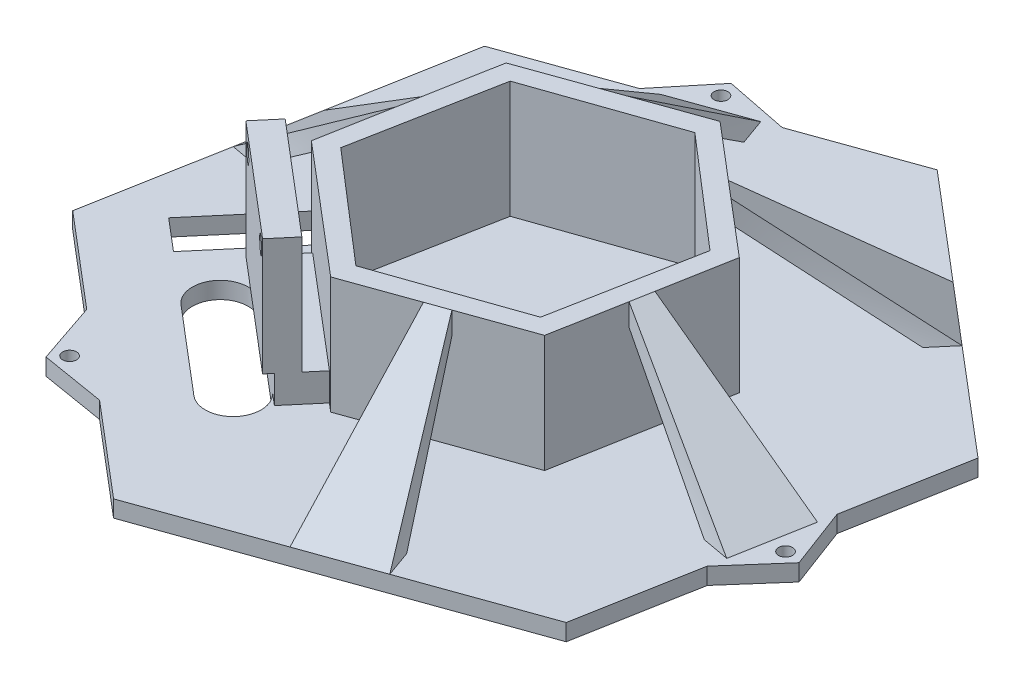
SolidWorks part; units mm, degrees
material "ABS"
ref_plane "Plan de face" through (0, 0, 0) normal (0, 0, 1) x (1, 0, 0)
ref_plane "Plan de dessus" through (0, 0, 0) normal (0, 1, 0) x (1, 0, 0)
ref_plane "Plan de droite" through (0, 0, 0) normal (1, 0, 0) x (0, 0, -1)
sketch "Esquisse1" plane through (0, 0, 0) normal (0, 1, 0) x (1, 0, 0)
  line L0 (-54.0644, 46.7159) -> (42.7784, -35.4763)
  line L1 (-54.0644, 46.7159) -> (-33.5846, 54.0399)
  line L2 (-54.0644, 46.7159) -> (-65.444, -15.7663)
  line L3 (-65.444, -15.7663) -> (-17.0226, -56.8624)
  line L4 (-17.0226, -56.8624) -> (42.7784, -35.4763)
  line L5 (42.7784, -35.4763) -> (54.1579, 27.0059)
  line L6 (54.1579, 27.0059) -> (5.7365, 68.102)
  line L7 (5.7365, 68.102) -> (-54.0644, 46.7159)
  line L8 (5.7365, 68.102) -> (-14.7432, 60.778)
  line L9 (-65.444, -15.7663) -> (-48.8613, -29.8403)
  line L10 (-17.0226, -56.8624) -> (-33.6053, -42.7884)
  line L11 (54.1579, 27.0059) -> (50.2608, 5.6079)
  line L12 (42.7784, -35.4763) -> (46.6755, -14.0783)
  line L13 (46.6755, -14.0783) -> (50.2608, 5.6079)
  line L14 (46.6755, -14.0783) -> (48.4681, -4.2352)
  line L15 (48.4681, -4.2352) -> (54.371, -5.3102)
  line L16 (54.371, -5.3102) -> (50.2608, 5.6079)
  line L17 (54.371, -5.3102) -> (46.6755, -14.0783)
  line L18 (-33.5846, 54.0399) -> (-24.1639, 57.409)
  line L19 (-24.1639, 57.409) -> (-26.1844, 63.0586)
  line L20 (-14.7432, 60.778) -> (-26.1844, 63.0586)
  line L21 (-33.5846, 54.0399) -> (-26.1844, 63.0586)
  line L22 (-48.8613, -29.8403) -> (-41.2333, -36.3143)
  line L23 (-41.2333, -36.3143) -> (-45.1158, -40.8889)
  line L24 (-45.1158, -40.8889) -> (-33.6053, -42.7884)
  line L25 (-45.1158, -40.8889) -> (-48.8613, -29.8403)
  line L26 (-24.1639, 57.409) -> (-25.1741, 60.2338)
  line L27 (48.4681, -4.2352) -> (51.4196, -4.7727)
  line L28 (-41.2333, -36.3143) -> (-43.1745, -38.6016)
  circle A0 centre (-5.643, 5.6198) radius 55.0013 construction
  circle A1 centre (-25.1741, 60.2338) radius 1.25
  circle A2 centre (51.4196, -4.7727) radius 1.25
  circle A3 centre (-43.1745, -38.6016) radius 1.25
extrude "Boss.-Extru.2" add sketch "Esquisse1" along normal blind 3 contours L3 L4 L0 L2 | A3 L23 L3 L25 | A3 L23 L24 L3 | L6 L7 L1 L0 L5 L13 | A2 L15 L16 L13 | A2 L15 L5 L17 | A1 L19 L7 L20 | A1 L19 L21 L7 region at (10.1749, 0, -24.2572) region at (-21.4609, 0, 13.0176) region at (-28.1828, 0, -58.0012) region at (49.7059, 0, 8.1043) region at (-21.432, 0, -60.4154) region at (-45.2029, 0, 35.4517) region at (-39.7367, 0, 40.0909) region at (50.9905, 0, 1.0508)
sketch "Esquisse2" plane through (0, 3, 0) normal (0, 1, 0) x (1, 0, 0)
  line L0 (-48.8613, -29.8403) -> (-65.444, -15.7663)
  line L1 (-65.444, -15.7663) -> (-17.0226, -56.8624)
  line L2 (-48.8613, -29.8403) -> (-41.0964, -20.6912)
  line L3 (-33.6053, -42.7884) -> (-25.8403, -33.6393)
  line L4 (-41.0964, -20.6912) -> (-25.8403, -33.6393)
  line L5 (-41.0964, -20.6912) -> (-34.6255, -13.067)
  line L6 (-25.8403, -33.6393) -> (-19.3695, -26.0151)
  line L7 (-34.6255, -13.067) -> (-19.3695, -26.0151)
  line L8 (-41.0964, -20.6912) -> (-48.8613, -29.8403)
  line L10 (-48.8613, -29.8403) -> (-65.444, -15.7663)
  line L11 (-41.6731, -13.6437) -> (-18.7928, -33.0626)
  line L12 (-57.679, -6.6172) -> (-65.444, -15.7663)
  line L13 (-26.9975, -19.5411) -> (-17.086, -27.9531)
  line L14 (-26.9975, -19.5411) -> (-36.909, -11.129)
  line L15 (-17.086, -27.9531) -> (-36.909, -11.129)
  line L16 (-17.086, -27.9531) -> (-14.9489, -25.435)
  line L17 (-36.909, -11.129) -> (-34.7718, -8.6109)
  line L18 (-14.9489, -25.435) -> (-34.7718, -8.6109)
  line L19 (-57.679, -6.6172) -> (-55.7348, -8.2673)
  line L20 (-34.6255, -13.067) -> (-41.0964, -20.6912)
  line L25 (-44.7374, 8.6312) -> (-37.1132, 2.1604)
  line L26 (-37.1132, 2.1604) -> (-50.0548, -13.088)
  line L27 (-50.0548, -13.088) -> (-57.679, -6.6172)
  line L28 (-55.7348, -8.2673) -> (-42.7932, 6.9811)
  arc A0 (-19.3695, -26.0151) -> (-25.8403, -33.6393) centre (-22.6049, -29.8272) cw
  arc A1 (-41.0964, -20.6912) -> (-34.6255, -13.067) centre (-37.8609, -16.8791) cw
  point P21 (-25.0563, -17.2538)
extrude "Enlèv. mat.-Extru.2" cut sketch "Esquisse2" against normal blind 5 contours L28 L27 L26 L25 | A1 L5 L11 | A1 L11 L5 | L5 L11 L6 L7 | L11 L5 L4 L6 | A0 L6 L11 | A0 L11 L6 region at (-46.424, 3, 3.0534) region at (-31.8506, 3, 25.2592) region at (-40.852, 3, 17.1239) region at (-22.3601, 3, 32.8183) region at (-38.1057, 3, 13.8881) region at (-28.6152, 3, 21.4471) region at (-19.6138, 3, 29.5824)
sketch "Esquisse3" plane through (0, 3, 0) normal (0, 1, 0) x (1, 0, 0)
  line L0 (-26.9975, -19.5411) -> (-36.909, -11.129)
  line L1 (-34.6255, -13.067) -> (-19.3695, -26.0151) construction
  line L2 (-26.9975, -19.5411) -> (-17.086, -27.9531)
  line L3 (-17.086, -27.9531) -> (-15.1448, -25.6658)
  line L4 (-15.1448, -25.6658) -> (-17.086, -27.9531)
  line L6 (-17.086, -27.9531) -> (-36.909, -11.129)
  line L7 (-34.9678, -8.8417) -> (-36.909, -11.129)
  line L8 (-17.086, -27.9531) -> (-36.909, -11.129)
  line L9 (-17.086, -27.9531) -> (-12.5565, -22.6162)
  line L10 (-36.909, -11.129) -> (-32.3794, -5.7921)
  line L11 (-12.5565, -22.6162) -> (-32.3794, -5.7921)
  line L12 (-36.909, -11.129) -> (-32.3794, -5.7921)
  line M31 (-34.6255, -13.067) -> (-19.3695, -26.0151)
extrude "Boss.-Extru.4" add sketch "Esquisse3" along normal blind 5 contours L9 L11 L10 L7 L0 L2 L3 M31 region at (-24.7327, 3, 16.8726)
sketch "Esquisse4" plane through (0, 8, 0) normal (0, 1, 0) x (1, 0, 0)
  line L0 (-14.8213, -25.2846) -> (-18.0567, -29.0967)
  line L1 (-17.086, -27.9531) -> (-12.5565, -22.6162) construction
  line L2 (-14.8213, -25.2846) -> (-34.6442, -8.4605)
  line L3 (-36.909, -11.129) -> (-32.3794, -5.7921) construction
  line L4 (-18.0567, -29.0967) -> (-14.8213, -25.2846)
  line L5 (-18.0567, -29.0967) -> (-37.8796, -12.2726)
  line L6 (-14.8213, -25.2846) -> (-34.6442, -8.4605)
  line L7 (-37.8796, -12.2726) -> (-34.6442, -8.4605)
  line M5 (-17.086, -27.9531) -> (-12.5565, -22.6162)
  line M7 (-32.3794, -5.7921) -> (-36.909, -11.129)
  line M8 (-36.909, -11.129) -> (-17.086, -27.9531)
extrude "Boss.-Extru.5" add sketch "Esquisse4" along normal blind 21 contours L2 M5 M7 M8 | L7 L5 L0 M8 region at (-25.8651, 8, 18.2068) region at (-27.4828, 8, 20.1129)
sketch "Esquisse5" plane through (0, 3, 0) normal (0, 1, 0) x (1, 0, 0)
  line L0 (5.7365, 68.102) -> (-17.0226, -56.8624)
  line L1 (-17.0226, -56.8624) -> (-65.444, -15.7663)
  line L2 (-65.444, -15.7663) -> (54.1579, 27.0059)
  line L3 (-32.3794, -5.7921) -> (-33.9133, -4.4902)
  line L4 (-33.9133, -4.4902) -> (-11.0226, -23.918)
  line L6 (-11.0226, -23.918) -> (17.2477, -13.8079)
  line L7 (17.2477, -13.8079) -> (22.6272, 15.7299)
  line L8 (22.6272, 15.7299) -> (-0.2635, 35.1576)
  line L9 (-0.2635, 35.1576) -> (-28.5337, 25.0476)
  line L10 (-28.5337, 25.0476) -> (-33.9133, -4.4902)
  line L11 (-33.9133, -4.4902) -> (-11.0226, -23.918)
  line L12 (14.0505, -11.3575) -> (18.9065, 14.1863)
  line L13 (18.9065, 14.1863) -> (-0.787, 31.1636)
  line L14 (-0.787, 31.1636) -> (-25.3366, 22.5971)
  line L15 (-25.3366, 22.5971) -> (-30.1926, -2.9467)
  line L16 (-30.1926, -2.9467) -> (-10.499, -19.924)
  line L17 (-10.499, -19.924) -> (14.0505, -11.3575)
  circle A0 centre (-5.643, 5.6198) radius 26.0013 construction
  circle A1 centre (-5.643, 5.6198) radius 22.5178 construction
  line M30 (-32.3794, -5.7921) -> (-12.5565, -22.6162)
extrude "Boss.-Extru.6" add sketch "Esquisse5" along normal blind 21 contours L16 L15 L14 L0 L9 L10 L2 | L14 L13 L2 L8 L0 | L17 L0 L6 L7 L2 L13 L12 | L17 L16 L2 L3 L4 L0 M30 region at (-21.4535, 3, 12.8347) region at (-10.1404, 3, 21.9762) region at (10.1675, 3, -24.0743) region at (-30.7119, 3, -10.1855)
sketch "Esquisse6" plane through (-32.033, 0, -5.834) normal (-0.9838, 0, -0.1792) x (-0.1792, 0, 0.9838)
  line L0 (-6.5178, 20) -> (-2.5178, 20)
  line L1 (-19.5296, 24) -> (10.4941, 24) construction
  line L6 (-6.5178, 20) -> (-6.5178, 24)
  line L7 (-6.5178, 24) -> (-2.5178, 24)
  line L8 (-2.5178, 24) -> (-2.5178, 20)
sketch "Esquisse7" plane through (0, 3, 0) normal (0, 1, 0) x (1, 0, 0)
  line L0 (-58.5, 22.3615) -> (-61.0084, 8.5881)
  line L4 (-58.5, 22.3615) -> (-53.5809, 21.4656)
  line L5 (-53.5809, 21.4656) -> (-56.0894, 7.6922)
  line L6 (-56.0894, 7.6922) -> (-61.0084, 8.5881)
sketch3d "Esquisse3D2"
  line L0 (-53.5809, 3, -21.4656) -> (-30.8652, 20, -12.2463)
  line L1 (-56.0894, 3, -7.6922) -> (-31.5819, 20, -8.311)
  line L2 (-58.5, 3, -22.3615) -> (-30.8652, 24, -12.2463)
  line L3 (-31.5819, 24, -8.311) -> (-61.0084, 3, -8.5881)
loft "Lissage1" add profiles "Esquisse7", "Esquisse6" connector at (-53.5809, 3, -21.4656) connector at (-30.8652, 20, -12.2463)
sketch "Esquisse8" plane through (-11.1773, 0, -31.2546) normal (-0.3367, 0, -0.9416) x (-0.9416, 0, 0.3367)
  line L1 (-11.5908, 24) -> (18.4329, 24) construction
  line L2 (1.4211, 20) -> (5.4211, 20)
  line L5 (1.4211, 20) -> (1.4211, 24)
  line L6 (1.4211, 24) -> (5.4211, 24)
  line L7 (5.4211, 24) -> (5.4211, 20)
sketch "Esquisse9" plane through (17.2346, 0, -20.3067) normal (0.6471, 0, -0.7624) x (-0.7624, 0, -0.6471)
  line L0 (5.9388, 20) -> (9.9388, 20)
  line L1 (-7.073, 24) -> (22.9507, 24) construction
  line L6 (5.9388, 20) -> (5.9388, 24)
  line L7 (5.9388, 24) -> (9.9388, 24)
  line L8 (9.9388, 24) -> (9.9388, 20)
sketch "Esquisse10" plane through (19.128, 0, 3.4837) normal (0.9838, 0, 0.1792) x (0.1792, 0, -0.9838)
  line L0 (2.5178, 20) -> (6.5178, 20)
  line L1 (2.5178, 24) -> (6.5178, 24)
  line L5 (2.5178, 20) -> (2.5178, 24)
  line L6 (6.5178, 20) -> (6.5178, 24)
sketch "Esquisse11" plane through (6.3338, 0, 17.711) normal (0.3367, 0, 0.9416) x (0.9416, 0, -0.3367)
  line L0 (-5.4211, 20) -> (-1.4211, 20)
  line L1 (-18.4329, 24) -> (11.5908, 24) construction
  line L5 (-5.4211, 20) -> (-5.4211, 24)
  line L6 (-5.4211, 24) -> (-1.4211, 24)
  line L7 (-1.4211, 24) -> (-1.4211, 20)
sketch "Esquisse12" plane through (0, 3, 0) normal (0, 1, 0) x (1, 0, 0)
  line L0 (-17.5727, 59.7661) -> (-30.7551, 55.0518)
  line L4 (-30.7551, 55.0518) -> (-29.0715, 50.3438)
  line L5 (-17.5727, 59.7661) -> (-15.8891, 55.0581)
  line L6 (-29.0715, 50.3438) -> (-15.8891, 55.0581)
sketch3d "Esquisse3D3"
  line L0 (-12.5154, 20, -30.7761) -> (-15.8891, 3, -55.0581)
  line L1 (-12.5154, 24, -30.7761) -> (-17.5727, 3, -59.7661)
  line L2 (-16.2818, 20, -29.4291) -> (-29.0715, 3, -50.3438)
  line L3 (-16.2818, 24, -29.4291) -> (-30.7551, 3, -55.0518)
loft "Lissage4" add profiles "Esquisse12", "Esquisse8" connector at (-17.5727, 3, -59.7661) connector at (-12.5154, 24, -30.7761)
sketch "Esquisse13" plane through (0, 3, 0) normal (0, 1, 0) x (1, 0, 0)
  line L0 (35.2842, 43.0244) -> (24.6103, 52.0835)
  line L1 (54.1579, 27.0059) -> (5.7365, 68.102) construction
  line L4 (35.2842, 43.0244) -> (32.0488, 39.2123)
  line L5 (21.3749, 48.2714) -> (24.6103, 52.0835)
  line L6 (32.0488, 39.2123) -> (21.3749, 48.2714)
loft "Lissage5" add profiles "Esquisse13", "Esquisse9" connector at (35.2842, 3, -43.0244) connector at (12.7067, 24, -24.1496)
sketch "Esquisse14" plane through (0, 3, 0) normal (0, 1, 0) x (1, 0, 0)
  line L0 (47.2139, -11.1219) -> (49.7224, 2.6515)
  line L4 (42.2948, -10.226) -> (47.2139, -11.1219)
  line L5 (49.7224, 2.6515) -> (44.8033, 3.5474)
  line L6 (44.8033, 3.5474) -> (42.2948, -10.226)
loft "Lissage6" add profiles "Esquisse10", "Esquisse14" connector at (19.5791, 20, 1.0067) connector at (42.2948, 3, 10.226)
sketch "Esquisse15" plane through (0, 3, 0) normal (0, 1, 0) x (1, 0, 0)
  line L0 (4.603, -43.8185) -> (17.7854, -39.1042)
  line L1 (-17.0226, -56.8624) -> (42.7784, -35.4763) construction
  line L5 (17.7854, -39.1042) -> (19.4691, -43.8122)
  line L6 (19.4691, -43.8122) -> (6.2867, -48.5265)
  line L7 (6.2867, -48.5265) -> (4.603, -43.8185)
loft "Lissage7" add profiles "Esquisse15", "Esquisse11" connector at (4.603, 3, 43.8185) connector at (1.2293, 20, 19.5364)
sketch "Esquisse16" plane through (-21.9154, 0, 25.8218) normal (-0.6471, 0, 0.7624) x (0.7624, 0, 0.6471)
  line L0 (-20.9388, 29) -> (-17.9388, 29)
  line L1 (5.0612, 29) -> (-20.9388, 29) construction
  line L2 (-17.9388, 29) -> (-17.9388, 26)
  line L3 (5.0612, 29) -> (2.0612, 29)
  line L4 (2.0612, 29) -> (2.0612, 26)
  circle A0 centre (-17.9388, 26) radius 1.5
  circle A1 centre (2.0612, 26) radius 1.5
extrude "Enlèv. mat.-Extru.3" cut sketch "Esquisse16" against normal blind 10 contours A0 | A1 region at (-36.3782, 24.9693, 13.547) region at (-21.1297, 24.9693, 26.4886)
